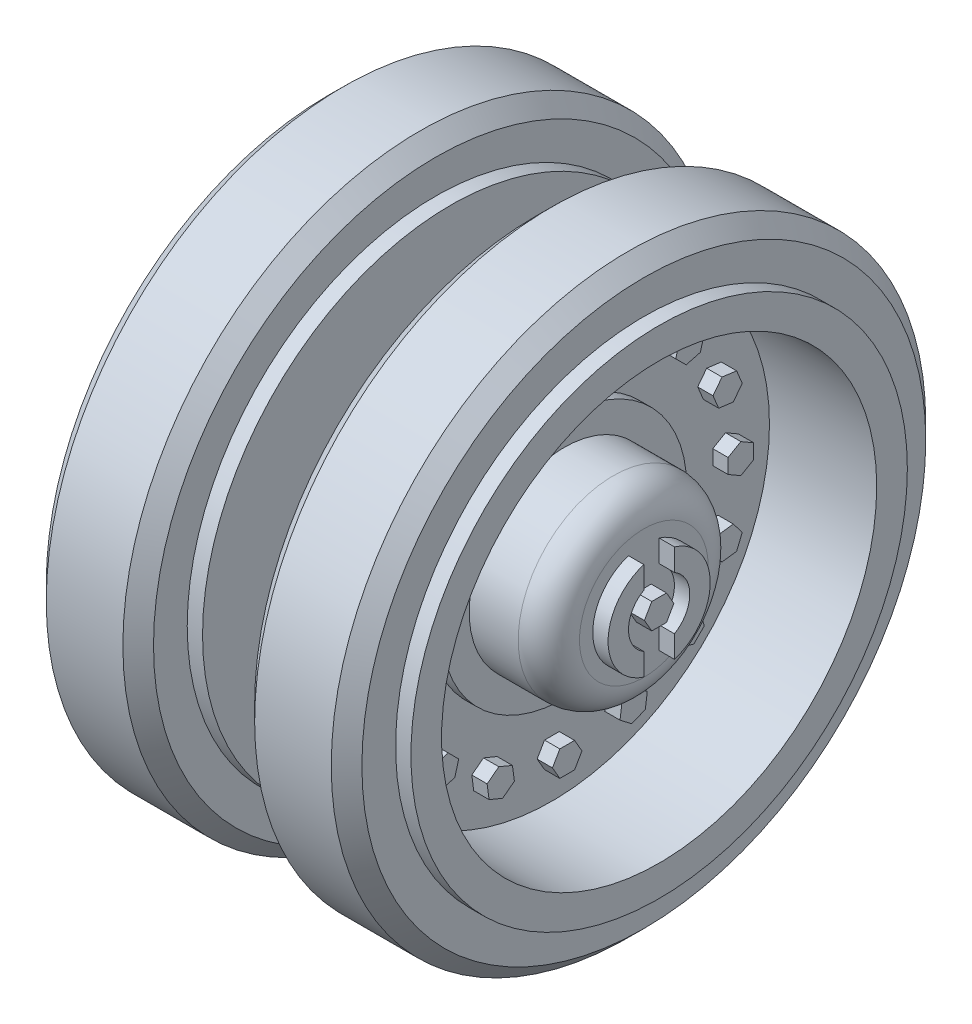
SolidWorks part; units mm, degrees
ref_plane "Ön Düzlem" through (0, 0, 0) normal (0, 0, 1) x (1, 0, 0)
ref_plane "Üst Düzlem" through (0, 0, 0) normal (0, 1, 0) x (1, 0, 0)
ref_plane "Sağ Düzlem" through (0, 0, 0) normal (1, 0, 0) x (0, 0, -1)
sketch "Çizim1" plane through (0, 0, 0) normal (1, 0, 0) x (0, 0, -1)
  circle A0 centre (0, 0) radius 243
  dimension "D1" = 486
extrude "Yükseklik-Ekstrüzyon1" add sketch "Çizim1" against normal blind 15
sketch "Çizim2" plane through (-15, 0, 0) normal (-1, 0, 0) x (0, 0, 1)
  circle A0 centre (0, 0) radius 291
  dimension "D1" = 582
extrude "Yükseklik-Ekstrüzyon2" add sketch "Çizim2" along normal blind 15
chamfer "Pah2" distance 15 angle 45 1 edges at (-15, 0, 291)
sketch "Çizim3" plane through (-30, 0, 0) normal (-1, 0, 0) x (0, 0, 1)
  circle A0 centre (0, 0) radius 291
extrude "Yükseklik-Ekstrüzyon3" add sketch "Çizim3" along normal blind 75
sketch "Çizim4" plane through (-105, 0, 0) normal (-1, 0, 0) x (0, 0, 1)
  circle A0 centre (0, 0) radius 291
extrude "Yükseklik-Ekstrüzyon4" add sketch "Çizim4" along normal blind 15
chamfer "Pah3" distance 15 angle 45 1 edges at (-120, 0, 291)
sketch "Çizim5" plane through (-120, 0, 0) normal (-1, 0, 0) x (0, 0, 1)
  circle A0 centre (0, 0) radius 243
  dimension "D1" = 486
extrude "Yükseklik-Ekstrüzyon5" add sketch "Çizim5" along normal blind 8
sketch "Çizim6" plane through (-128, 0, 0) normal (-1, 0, 0) x (0, 0, 1)
  circle A0 centre (0, 0) radius 153
  dimension "D1" = 306
extrude "Yükseklik-Ekstrüzyon6" add sketch "Çizim6" along normal blind 76
sketch "Çizim7" plane through (-204, 0, 0) normal (-1, 0, 0) x (0, 0, 1)
  circle A0 centre (0, 0) radius 243
  dimension "D1" = 486
extrude "Yükseklik-Ekstrüzyon7" add sketch "Çizim7" along normal blind 15
sketch "Çizim8" plane through (-219, 0, 0) normal (-1, 0, 0) x (0, 0, 1)
  circle A0 centre (0, 0) radius 291
  dimension "D1" = 582
extrude "Yükseklik-Ekstrüzyon8" add sketch "Çizim8" along normal blind 15
chamfer "Pah4" distance 15 angle 45 1 edges at (-219, 0, 291)
sketch "Çizim9" plane through (-234, 0, 0) normal (-1, 0, 0) x (0, 0, 1)
  circle A0 centre (0, 0) radius 291
extrude "Yükseklik-Ekstrüzyon9" add sketch "Çizim9" along normal blind 75
sketch "Çizim10" plane through (-309, 0, 0) normal (-1, 0, 0) x (0, 0, 1)
  circle A0 centre (0, 0) radius 291
extrude "Yükseklik-Ekstrüzyon10" add sketch "Çizim10" along normal blind 15
chamfer "Pah5" distance 15 angle 45 1 edges at (-324, 0, 291)
sketch "Çizim11" plane through (-324, 0, 0) normal (-1, 0, 0) x (0, 0, 1)
  circle A0 centre (0, 0) radius 243
  dimension "D1" = 486
extrude "Yükseklik-Ekstrüzyon11" add sketch "Çizim11" along normal blind 8
sketch "Çizim12" plane through (-332, 0, 0) normal (-1, 0, 0) x (0, 0, 1)
  circle A0 centre (0, 0) radius 93
  circle A1 centre (0, 0) radius 213
  dimension "D1" = 186
  dimension "D2" = 426
extrude "Kes-Ekstrüzyon1" cut sketch "Çizim12" against normal blind 105
sketch "Çizim13" plane through (-332, 0, 0) normal (-1, 0, 0) x (0, 0, 1)
  circle A0 centre (0, 0) radius 45
  dimension "D1" = 90
extrude "Kes-Ekstrüzyon2" cut sketch "Çizim13" against normal blind 150
sketch "Çizim14" plane through (-182, 0, 0) normal (-1, 0, 0) x (0, 0, 1)
  circle A0 centre (0, 0) radius 27
  dimension "D1" = 54
extrude "Kes-Ekstrüzyon3" cut sketch "Çizim14" against normal blind 120
sketch "Çizim15" plane through (0, 0, 0) normal (1, 0, 0) x (0, 0, -1)
  circle A0 centre (0, 0) radius 93
  circle A1 centre (0, 0) radius 120
  dimension "D1" = 186
  dimension "D2" = 240
extrude "Kes-Ekstrüzyon4" cut sketch "Çizim15" against normal blind 93
sketch "Çizim16" plane through (0, 0, 0) normal (1, 0, 0) x (0, 0, -1)
  circle A0 centre (0, 0) radius 120
  circle A1 centre (0, 0) radius 213
  dimension "D1" = 240
  dimension "D2" = 426
extrude "Kes-Ekstrüzyon5" cut sketch "Çizim16" against normal blind 105
sketch "Çizim17" plane through (-105, 0, 0) normal (1, 0, 0) x (0, 0, -1)
  line L0 (78.3912, 151.536) -> (76.5073, 165.8462)
  line L1 (14.4338, 170) -> (7.2169, 182.5)
  line L2 (7.2169, 182.5) -> (-7.2169, 182.5)
  line L3 (-7.2169, 182.5) -> (-14.4338, 170)
  line L4 (-14.4338, 170) -> (-7.2169, 157.5)
  line L5 (-7.2169, 157.5) -> (7.2169, 157.5)
  line L6 (7.2169, 157.5) -> (14.4338, 170)
  line L7 (76.5073, 165.8462) -> (63.1722, 171.3698)
  line L8 (63.1722, 171.3698) -> (51.7211, 162.5831)
  line L9 (51.7211, 162.5831) -> (53.6051, 148.2728)
  line L10 (53.6051, 148.2728) -> (66.9402, 142.7492)
  line L11 (66.9402, 142.7492) -> (78.3912, 151.536)
  line L12 (130.4144, 110.0019) -> (134.1501, 123.9439)
  line L13 (134.1501, 123.9439) -> (123.9439, 134.1501)
  line L14 (123.9439, 134.1501) -> (110.0019, 130.4144)
  line L15 (110.0019, 130.4144) -> (106.2662, 116.4724)
  line L16 (106.2662, 116.4724) -> (116.4724, 106.2662)
  line L17 (116.4724, 106.2662) -> (130.4144, 110.0019)
  line L18 (162.5831, 51.7211) -> (171.3698, 63.1722)
  line L19 (171.3698, 63.1722) -> (165.8462, 76.5073)
  line L20 (165.8462, 76.5073) -> (151.536, 78.3912)
  line L21 (151.536, 78.3912) -> (142.7492, 66.9402)
  line L22 (142.7492, 66.9402) -> (148.2728, 53.6051)
  line L23 (148.2728, 53.6051) -> (162.5831, 51.7211)
  line L24 (170, -14.4338) -> (182.5, -7.2169)
  line L25 (182.5, -7.2169) -> (182.5, 7.2169)
  line L26 (182.5, 7.2169) -> (170, 14.4338)
  line L27 (170, 14.4338) -> (157.5, 7.2169)
  line L28 (157.5, 7.2169) -> (157.5, -7.2169)
  line L29 (157.5, -7.2169) -> (170, -14.4338)
  line L30 (151.536, -78.3912) -> (165.8462, -76.5073)
  line L31 (165.8462, -76.5073) -> (171.3698, -63.1722)
  line L32 (171.3698, -63.1722) -> (162.5831, -51.7211)
  line L33 (162.5831, -51.7211) -> (148.2728, -53.6051)
  line L34 (148.2728, -53.6051) -> (142.7492, -66.9402)
  line L35 (142.7492, -66.9402) -> (151.536, -78.3912)
  line L36 (110.0019, -130.4144) -> (123.9439, -134.1501)
  line L37 (123.9439, -134.1501) -> (134.1501, -123.9439)
  line L38 (134.1501, -123.9439) -> (130.4144, -110.0019)
  line L39 (130.4144, -110.0019) -> (116.4724, -106.2662)
  line L40 (116.4724, -106.2662) -> (106.2662, -116.4724)
  line L41 (106.2662, -116.4724) -> (110.0019, -130.4144)
  line L42 (51.7211, -162.5831) -> (63.1722, -171.3698)
  line L43 (63.1722, -171.3698) -> (76.5073, -165.8462)
  line L44 (76.5073, -165.8462) -> (78.3912, -151.536)
  line L45 (78.3912, -151.536) -> (66.9402, -142.7492)
  line L46 (66.9402, -142.7492) -> (53.6051, -148.2728)
  line L47 (53.6051, -148.2728) -> (51.7211, -162.5831)
  line L48 (-14.4338, -170) -> (-7.2169, -182.5)
  line L49 (-7.2169, -182.5) -> (7.2169, -182.5)
  line L50 (7.2169, -182.5) -> (14.4338, -170)
  line L51 (14.4338, -170) -> (7.2169, -157.5)
  line L52 (7.2169, -157.5) -> (-7.2169, -157.5)
  line L53 (-7.2169, -157.5) -> (-14.4338, -170)
  line L54 (-78.3912, -151.536) -> (-76.5073, -165.8462)
  line L55 (-76.5073, -165.8462) -> (-63.1722, -171.3698)
  line L56 (-63.1722, -171.3698) -> (-51.7211, -162.5831)
  line L57 (-51.7211, -162.5831) -> (-53.6051, -148.2728)
  line L58 (-53.6051, -148.2728) -> (-66.9402, -142.7492)
  line L59 (-66.9402, -142.7492) -> (-78.3912, -151.536)
  line L60 (-130.4144, -110.0019) -> (-134.1501, -123.9439)
  line L61 (-134.1501, -123.9439) -> (-123.9439, -134.1501)
  line L62 (-123.9439, -134.1501) -> (-110.0019, -130.4144)
  line L63 (-110.0019, -130.4144) -> (-106.2662, -116.4724)
  line L64 (-106.2662, -116.4724) -> (-116.4724, -106.2662)
  line L65 (-116.4724, -106.2662) -> (-130.4144, -110.0019)
  line L66 (-162.5831, -51.7211) -> (-171.3698, -63.1722)
  line L67 (-171.3698, -63.1722) -> (-165.8462, -76.5073)
  line L68 (-165.8462, -76.5073) -> (-151.536, -78.3912)
  line L69 (-151.536, -78.3912) -> (-142.7492, -66.9402)
  line L70 (-142.7492, -66.9402) -> (-148.2728, -53.6051)
  line L71 (-148.2728, -53.6051) -> (-162.5831, -51.7211)
  line L72 (-170, 14.4338) -> (-182.5, 7.2169)
  line L73 (-182.5, 7.2169) -> (-182.5, -7.2169)
  line L74 (-182.5, -7.2169) -> (-170, -14.4338)
  line L75 (-170, -14.4338) -> (-157.5, -7.2169)
  line L76 (-157.5, -7.2169) -> (-157.5, 7.2169)
  line L77 (-157.5, 7.2169) -> (-170, 14.4338)
  line L78 (-151.536, 78.3912) -> (-165.8462, 76.5073)
  line L79 (-165.8462, 76.5073) -> (-171.3698, 63.1722)
  line L80 (-171.3698, 63.1722) -> (-162.5831, 51.7211)
  line L81 (-162.5831, 51.7211) -> (-148.2728, 53.6051)
  line L82 (-148.2728, 53.6051) -> (-142.7492, 66.9402)
  line L83 (-142.7492, 66.9402) -> (-151.536, 78.3912)
  line L84 (-110.0019, 130.4144) -> (-123.9439, 134.1501)
  line L85 (-123.9439, 134.1501) -> (-134.1501, 123.9439)
  line L86 (-134.1501, 123.9439) -> (-130.4144, 110.0019)
  line L87 (-130.4144, 110.0019) -> (-116.4724, 106.2662)
  line L88 (-116.4724, 106.2662) -> (-106.2662, 116.4724)
  line L89 (-106.2662, 116.4724) -> (-110.0019, 130.4144)
  line L90 (-51.7211, 162.5831) -> (-63.1722, 171.3698)
  line L91 (-63.1722, 171.3698) -> (-76.5073, 165.8462)
  line L92 (-76.5073, 165.8462) -> (-78.3912, 151.536)
  line L93 (-78.3912, 151.536) -> (-66.9402, 142.7492)
  line L94 (-66.9402, 142.7492) -> (-53.6051, 148.2728)
  line L95 (-53.6051, 148.2728) -> (-51.7211, 162.5831)
  circle A0 centre (0, 0) radius 170 construction
  circle A1 centre (0, 170) radius 12.5 construction
  circle A2 centre (65.0562, 157.0595) radius 12.5 construction
  circle A3 centre (120.2082, 120.2082) radius 12.5 construction
  circle A4 centre (157.0595, 65.0562) radius 12.5 construction
  circle A5 centre (170, 0) radius 12.5 construction
  circle A6 centre (157.0595, -65.0562) radius 12.5 construction
  circle A7 centre (120.2082, -120.2082) radius 12.5 construction
  circle A8 centre (65.0562, -157.0595) radius 12.5 construction
  circle A9 centre (0, -170) radius 12.5 construction
  circle A10 centre (-65.0562, -157.0595) radius 12.5 construction
  circle A11 centre (-120.2082, -120.2082) radius 12.5 construction
  circle A12 centre (-157.0595, -65.0562) radius 12.5 construction
  circle A13 centre (-170, 0) radius 12.5 construction
  circle A14 centre (-157.0595, 65.0562) radius 12.5 construction
  circle A15 centre (-120.2082, 120.2082) radius 12.5 construction
  circle A16 centre (-65.0562, 157.0595) radius 12.5 construction
  point P134 (0, 0)
  dimension "D1" = 340
  dimension "D2" = 25
  dimension "D3" = 16
extrude "Yükseklik-Ekstrüzyon12" add sketch "Çizim17" along normal blind 15
sketch "Çizim19" plane through (0, 0, 0) normal (1, 0, 0) x (0, 0, -1)
  circle A0 centre (0, 0) radius 93
extrude "Kes-Ekstrüzyon8" cut sketch "Çizim19" against normal blind 15
sketch "Çizim20" plane through (-15, 0, 0) normal (1, 0, 0) x (0, 0, -1)
  line L0 (0, 0) -> (-15, 0) construction
  line L1 (0, 0) -> (15, 0) construction
  line L2 (-15, 25.9808) -> (-15, 47.697)
  line L3 (15, 25.9808) -> (15, 47.697)
  line L4 (15, -25.9808) -> (15, -47.697)
  line L5 (-15, -25.9808) -> (-15, -47.697)
  arc A0 (15, -25.9808) -> (15, 25.9808) centre (0, 0) ccw
  arc A1 (15, -47.697) -> (15, 47.697) centre (0, 0) ccw
  arc A2 (-15, 25.9808) -> (-15, -25.9808) centre (0, 0) ccw
  arc A3 (-15, 47.697) -> (-15, -47.697) centre (0, 0) ccw
  dimension "D1" = 60
  dimension "D2" = 100
  dimension "D3" = 15
  dimension "D4" = 15
extrude "Yükseklik-Ekstrüzyon13" add sketch "Çizim20" along normal blind 15
sketch "Çizim21" plane through (-15, 0, 0) normal (1, 0, 0) x (0, 0, -1)
  line L1 (14.4338, 0) -> (7.2169, 12.5)
  line L2 (7.2169, 12.5) -> (-7.2169, 12.5)
  line L3 (-7.2169, 12.5) -> (-14.4338, 0)
  line L4 (-14.4338, 0) -> (-7.2169, -12.5)
  line L5 (-7.2169, -12.5) -> (7.2169, -12.5)
  line L6 (7.2169, -12.5) -> (14.4338, 0)
  circle A0 centre (0, 0) radius 12.5 construction
  dimension "D1" = 25
extrude "Yükseklik-Ekstrüzyon14" add sketch "Çizim21" along normal blind 15
fillet "Radyus2" radius 30 1 edges at (-15, 0, -93)
